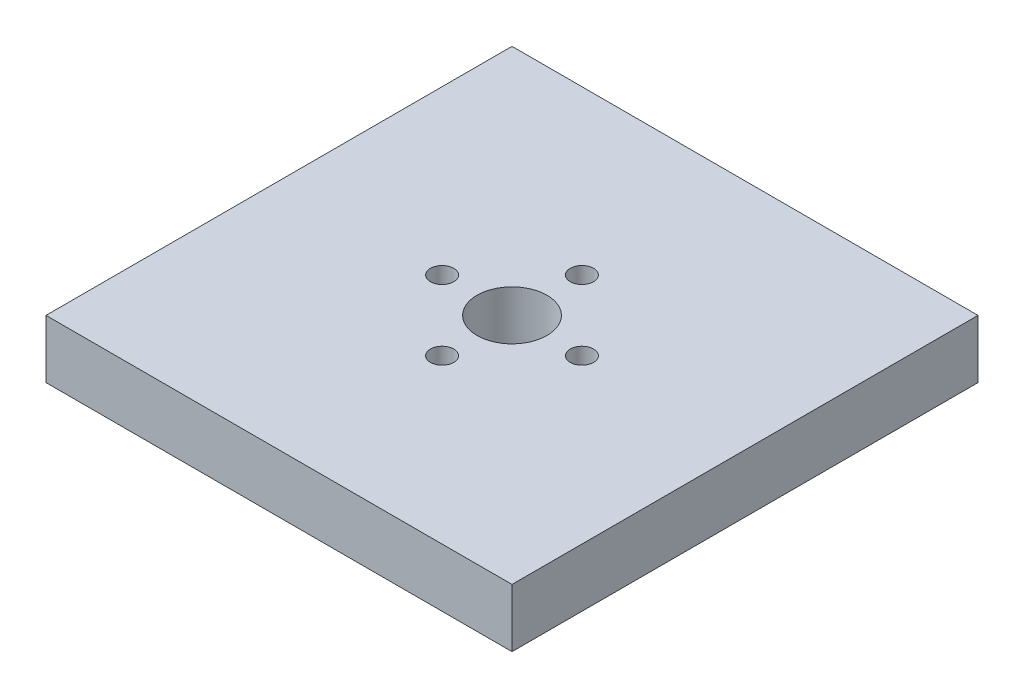
SolidWorks part; units mm, degrees
ref_plane "Front Plane" through (0, 0, 0) normal (0, 0, 1) x (1, 0, 0)
ref_plane "Top Plane" through (0, 0, 0) normal (0, 1, 0) x (1, 0, 0)
ref_plane "Right Plane" through (0, 0, 0) normal (1, 0, 0) x (0, 0, -1)
sketch "Sketch1" plane through (0, 0, 0) normal (0, 1, 0) x (1, 0, 0)
  line L1 (0, 0) -> (40, 0)
  line L2 (0, 0) -> (0, 40)
  line L3 (0, 40) -> (40, 40)
  line L4 (40, 0) -> (40, 40)
  dimension "D1" = 40
  dimension "D2" = 40
extrude "Boss-Extrude1" add sketch "Sketch1" along normal blind 5
sketch "Sketch8" plane through (0, 5, 0) normal (0, 1, 0) x (1, 0, 0)
  line L2 (0, 40) -> (0, 0) construction
  line L3 (40, 40) -> (0, 40) construction
  line L5 (40, 0) -> (40, 40) construction
  line L6 (0, 0) -> (40, 0) construction
  circle A0 centre (20, 20) radius 3
  circle A1 centre (20, 14) radius 1
  circle A2 centre (26, 20) radius 1
  circle A3 centre (14, 20) radius 1
  circle A4 centre (20, 26) radius 1
  point P11 (14.168, 10.4582)
  point P19 (19.2131, 14.6171)
  dimension "D3" = 6
  dimension "D4" = 20
  dimension "D1" = 20
  dimension "D2" = 20
  dimension "D5" = 6
  dimension "D6" = 20
  dimension "D7" = 20
  dimension "D8" = 14
  dimension "D9" = 20
extrude "Cut-Extrude4" cut sketch "Sketch8" against normal blind 15 and the other way blind 15
